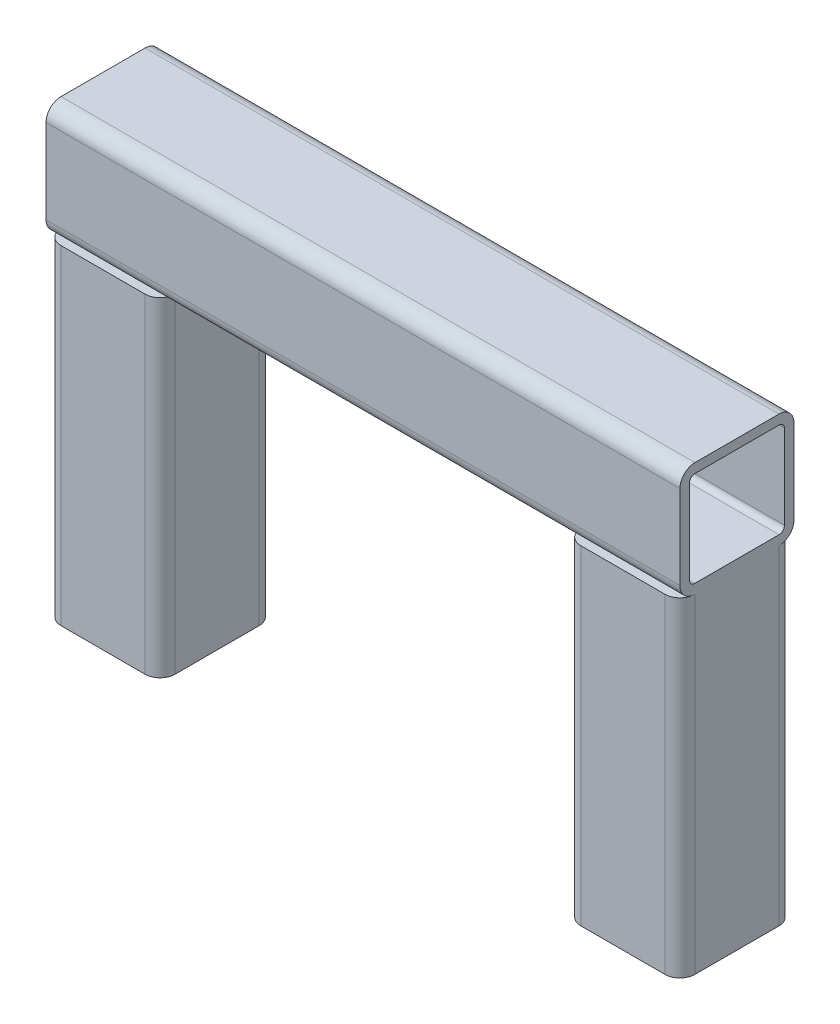
SolidWorks part; units mm, degrees
ref_plane "Front Plane" through (0, 0, 0) normal (0, 0, 1) x (1, 0, 0)
ref_plane "Top Plane" through (0, 0, 0) normal (0, 1, 0) x (1, 0, 0)
ref_plane "Right Plane" through (0, 0, 0) normal (1, 0, 0) x (0, 0, -1)
sketch "Sketch1" plane through (0, 0, 0) normal (0, 1, 0) x (1, 0, 0)
  line L0 (-14.05, 19.05) -> (14.05, 19.05)
  line L1 (19.05, 14.05) -> (19.05, -14.05)
  line L2 (-15.875, 14.05) -> (-15.875, -14.05)
  line L3 (-14.05, -15.875) -> (14.05, -15.875)
  line L4 (14.05, -19.05) -> (-14.05, -19.05)
  line L5 (-19.05, -14.05) -> (-19.05, 14.05)
  line L6 (0, 19.05) -> (0, -19.05) construction
  line L7 (-19.05, 0) -> (19.05, 0) construction
  line L8 (15.875, -14.05) -> (15.875, 14.05)
  line L9 (14.05, 15.875) -> (-14.05, 15.875)
  line L10 (0, 15.875) -> (0, -15.875) construction
  line L11 (-15.875, 0) -> (15.875, 0) construction
  arc A0 (14.05, 19.05) -> (19.05, 14.05) centre (14.05, 14.05) cw
  arc A1 (19.05, -14.05) -> (14.05, -19.05) centre (14.05, -14.05) cw
  arc A2 (-14.05, -19.05) -> (-19.05, -14.05) centre (-14.05, -14.05) cw
  arc A3 (-19.05, 14.05) -> (-14.05, 19.05) centre (-14.05, 14.05) cw
  arc A4 (-15.875, -14.05) -> (-14.05, -15.875) centre (-14.05, -14.05) ccw
  arc A5 (14.05, -15.875) -> (15.875, -14.05) centre (14.05, -14.05) ccw
  arc A6 (15.875, 14.05) -> (14.05, 15.875) centre (14.05, 14.05) ccw
  arc A7 (-14.05, 15.875) -> (-15.875, 14.05) centre (-14.05, 14.05) ccw
  point P33 (0, 0)
  dimension "D1" = 5
  dimension "D2" = 3.175
  dimension "D3" = 38.1
extrude "Boss-Extrude1" add sketch "Sketch1" along normal blind 110
ref_plane "Plane1" through (86.85, 0, 0) normal (1, 0, 0) x (0, 0, -1)
mirror "Mirror2" about plane through (86.85, 0, 0) normal (1, 0, 0) of bodies 101
sketch "Sketch2" plane through (86.85, 0, 0) normal (1, 0, 0) x (0, 0, -1)
  line L0 (-14.05, 148.1) -> (14.05, 148.1)
  line L1 (19.05, 143.1) -> (19.05, 115)
  line L2 (-15.875, 143.1) -> (-15.875, 115)
  line L3 (-14.05, 113.175) -> (14.05, 113.175)
  line L4 (14.05, 110) -> (-14.05, 110)
  line L5 (-19.05, 115) -> (-19.05, 143.1)
  line L6 (0, 148.1) -> (0, 110) construction
  line L7 (-19.05, 129.05) -> (19.05, 129.05) construction
  line L8 (15.875, 115) -> (15.875, 143.1)
  line L9 (14.05, 144.925) -> (-14.05, 144.925)
  line L10 (0, 144.925) -> (0, 113.175) construction
  line L11 (-15.875, 129.05) -> (15.875, 129.05) construction
  line L12 (0, 55) -> (0, -55) construction
  line L13 (14.05, 110) -> (-14.05, 110) construction
  arc A0 (14.05, 148.1) -> (19.05, 143.1) centre (14.05, 143.1) cw
  arc A1 (19.05, 115) -> (14.05, 110) centre (14.05, 115) cw
  arc A2 (-14.05, 110) -> (-19.05, 115) centre (-14.05, 115) cw
  arc A3 (-19.05, 143.1) -> (-14.05, 148.1) centre (-14.05, 143.1) cw
  arc A4 (-15.875, 115) -> (-14.05, 113.175) centre (-14.05, 115) ccw
  arc A5 (14.05, 113.175) -> (15.875, 115) centre (14.05, 115) ccw
  arc A6 (15.875, 143.1) -> (14.05, 144.925) centre (14.05, 143.1) ccw
  arc A7 (-14.05, 144.925) -> (-15.875, 143.1) centre (-14.05, 143.1) ccw
  dimension "D1" = 5
  dimension "D2" = 3.175
  dimension "D3" = 38.1
extrude "Boss-Extrude2" add sketch "Sketch2" along normal up to surface (105.9 mm away) and the other way up to surface (105.9 mm away) up to face at (192.75, 55, 0) other way up to face at (-19.05, 55, 0)
